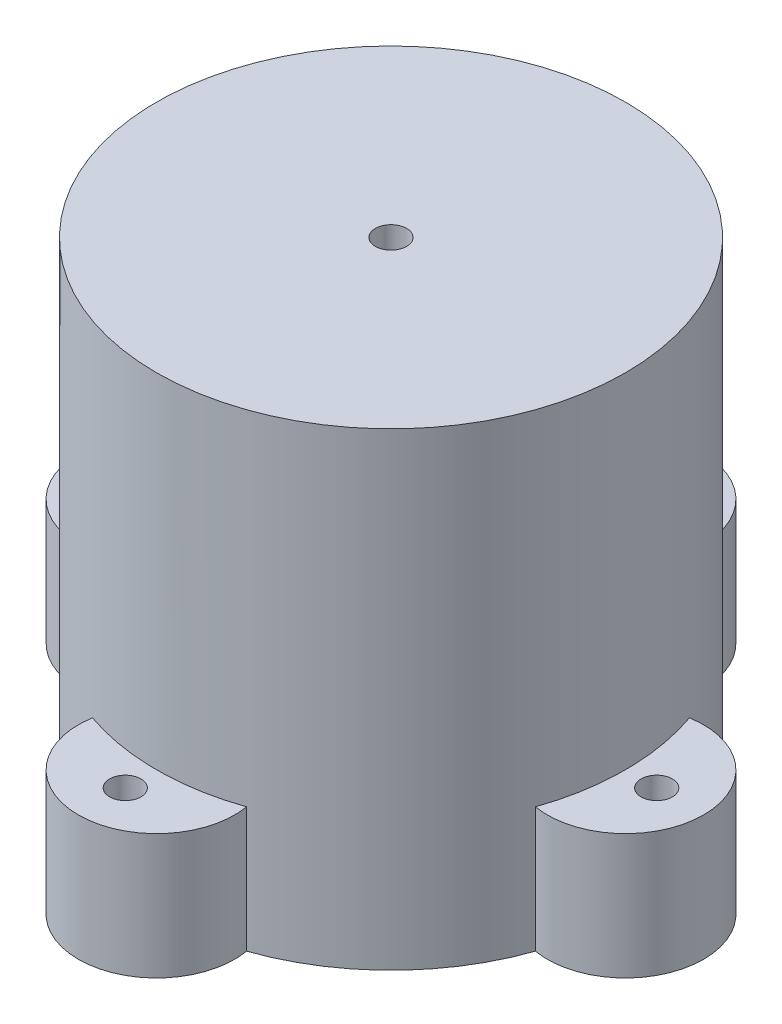
SolidWorks part; units mm, degrees
ref_plane "Front Plane" through (0, 0, 0) normal (0, 0, 1) x (1, 0, 0)
ref_plane "Top Plane" through (0, 0, 0) normal (0, 1, 0) x (1, 0, 0)
ref_plane "Right Plane" through (0, 0, 0) normal (1, 0, 0) x (0, 0, -1)
sketch "Sketch1" plane through (0, 0, 0) normal (0, 1, 0) x (1, 0, 0)
  arc A0 (-35.4167, -12.3252) -> (-12.3252, -35.4167) centre (0, 0) ccw
  arc A1 (12.3252, 35.4167) -> (-12.3252, 35.4167) centre (0, 37.5) ccw
  arc A2 (-35.4167, 12.3252) -> (-35.4167, -12.3252) centre (-37.5, 0) ccw
  arc A3 (-12.3252, -35.4167) -> (12.3252, -35.4167) centre (0, -37.5) ccw
  arc A4 (35.4167, -12.3252) -> (35.4167, 12.3252) centre (37.5, 0) ccw
  arc A5 (-12.3252, 35.4167) -> (-35.4167, 12.3252) centre (0, 0) ccw
  arc A6 (35.4167, 12.3252) -> (12.3252, 35.4167) centre (0, 0) ccw
  arc A7 (12.3252, -35.4167) -> (35.4167, -12.3252) centre (0, 0) ccw
  circle A8 centre (0, 0) radius 2.5
  circle A9 centre (-42.5, 0) radius 2.5
  circle A10 centre (0, 42.5) radius 2.5
  circle A11 centre (42.5, 0) radius 2.5
  circle A12 centre (0, -42.5) radius 2.5
  circle A13 centre (0, 0) radius 37.5
  dimension "D1" = 75
  dimension "D2" = 25
  dimension "D3" = 5
  dimension "D4" = 5
  dimension "D5" = 5
  dimension "D6" = 5
  dimension "D7" = 5
  dimension "D8" = 5
extrude "Boss-Extrude1" add sketch "Sketch1" along normal blind 75 contours A7 A13 A6 A5 A0 A8 region at (-36.4393, 0, 0)
extrude "Boss-Extrude2" add sketch "Sketch1<3>" along normal blind 20 contours A13 A2 A9 | A13 A3 A12 | A13 A4 A11 | A13 A1 A10 region at (-49.7106, 0, 0) region at (0, 0, 37.7894) region at (0, 0, -49.7106) region at (37.2609, 0, 6.2982)
sketch "Sketch1<3>" plane through (0, 0, 0) normal (0, 1, 0) x (1, 0, 0) same geometry as "Sketch1"
